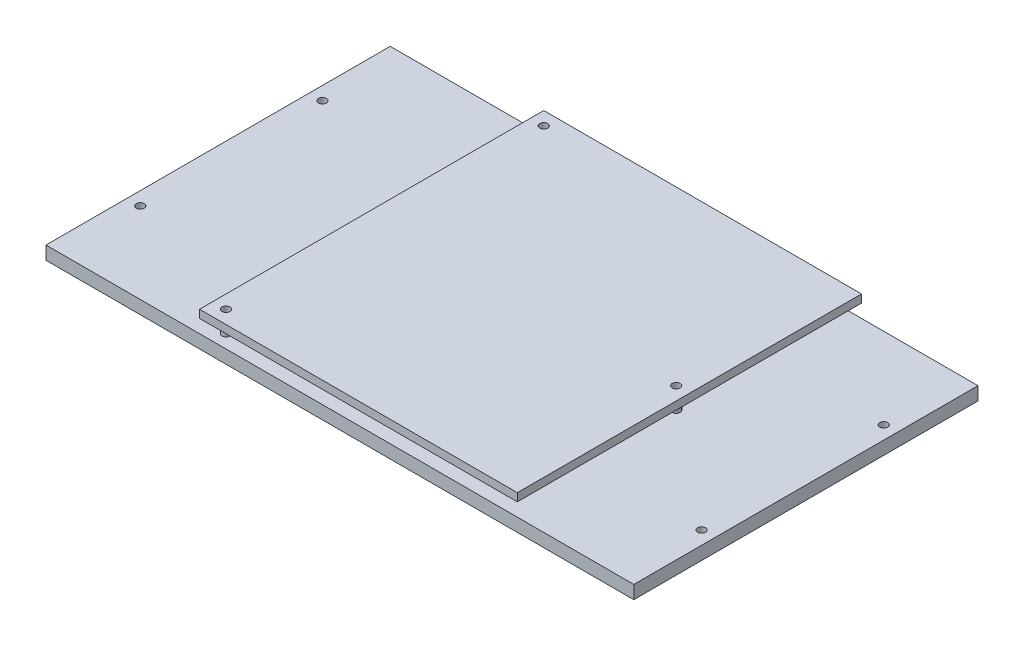
SolidWorks part; units mm, degrees
material "Teca"
ref_plane "Plano frontal" through (0, 0, 0) normal (0, 0, 1) x (1, 0, 0)
ref_plane "Plano superior" through (0, 0, 0) normal (0, 1, 0) x (1, 0, 0)
ref_plane "Plano direito" through (0, 0, 0) normal (1, 0, 0) x (0, 0, -1)
sketch "Esboço1" plane through (0, 0, 0) normal (0, 1, 0) x (1, 0, 0)
  line L0 (106, 34.4) -> (106, -34.4) construction
  line L1 (-111, 65) -> (111, 65)
  line L2 (-111, 65) -> (-111, -65)
  line L3 (-111, -65) -> (111, -65)
  line L4 (111, 65) -> (111, -65)
  line L5 (-111, 65) -> (111, -65) construction
  line L6 (-111, -65) -> (111, 65) construction
  line L7 (106, 34.4) -> (-106, 34.4) construction
  line L8 (106, -34.4) -> (-106, -34.4) construction
  circle A0 centre (-106, 34.4) radius 1.5
  circle A1 centre (-106, -34.4) radius 1.5
  circle A2 centre (106, 34.4) radius 1.5
  circle A3 centre (106, -34.4) radius 1.5
  point P0 (0, 0)
  dimension "D4" = 5
  dimension "D5" = 3
  dimension "D6" = 99.4
  dimension "D8" = 3
  dimension "D9" = 3
  dimension "D10" = 3
  dimension "D1" = 222
  dimension "D2" = 130
  dimension "D3" = 30.6
  dimension "D7" = 5
  dimension "D11" = 5
extrude "Ressalto-extrusão1" add sketch "Esboço1" along normal blind 5
sketch "Esboço2" plane through (0, 5, 0) normal (0, 1, 0) x (1, 0, 0)
  line L0 (-111, -65) -> (111, -65) construction
  line L1 (-53, 65) -> (67, 65)
  line L2 (-53, 65) -> (-53, -65)
  line L3 (-53, -65) -> (67, -65)
  line L4 (67, 65) -> (67, -65)
  line L5 (-111, 65) -> (-111, -65) construction
  line L6 (0, 0) -> (62, 0) construction
  circle A0 centre (-48, -60) radius 1.5
  circle A1 centre (62, 0) radius 1.5
  circle A2 centre (-48, 60) radius 1.5
  dimension "D4" = 3
  dimension "D5" = 3
  dimension "D6" = 3
  dimension "D8" = 5
  dimension "D9" = 5
  dimension "D10" = 5
  dimension "D11" = 5
  dimension "D1" = 130
  dimension "D2" = 120
  dimension "D3" = 58
  dimension "D7" = 5
extrude "Ressalto-extrusão2" add sketch "Esboço2" along normal blind 5 contours A1 | A0 | A2 region at (-48, 5, 60) region at (62, 5, 0)
extrude "Ressalto-extrusão3" add sketch "Esboço2<3>" along normal blind 3 from offset 5 separate body
sketch "Esboço2<3>" plane through (0, 5, 0) normal (0, 1, 0) x (1, 0, 0) same geometry as "Esboço2"
